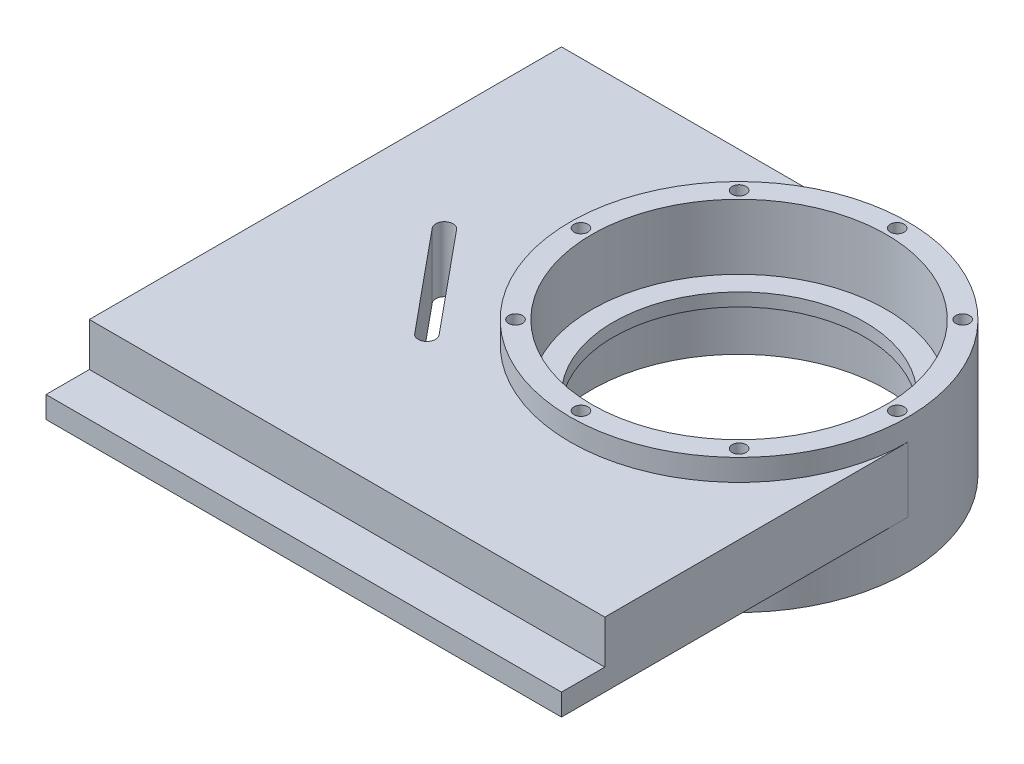
SolidWorks part; units mm, degrees
ref_plane "Front Plane" through (0, 0, 0) normal (0, 0, 1) x (1, 0, 0)
ref_plane "Top Plane" through (0, 0, 0) normal (0, 1, 0) x (1, 0, 0)
ref_plane "Right Plane" through (0, 0, 0) normal (1, 0, 0) x (0, 0, -1)
sketch "Sketch2" plane through (0, 0, 0) normal (0, 1, 0) x (1, 0, 0)
  line L0 (0, 0) -> (0, -80) construction
  line L1 (0, 39) -> (-80, 39)
  line L2 (-80, 39) -> (-80, -80)
  line L3 (-80, -80) -> (0, -80)
  line L4 (39, 0) -> (39, -80)
  line L5 (39, -80) -> (0, -80)
  circle A0 centre (0, 0) radius 22.5 construction
  circle A1 centre (0, 0) radius 34
  circle A2 centre (0, 0) radius 29
  circle A3 centre (0, 0) radius 39
  dimension "D1" = 80
  dimension "D2" = 68
  dimension "D3" = 45
  dimension "D4" = 58
  dimension "D7" = 78
  dimension "D6" = 80
  dimension "D5" = 5
extrude "Boss-Extrude1" add sketch "Sketch2" along normal blind 15 contours A3 A1 region at (26.7972, 0, -26.7972)
extrude "Boss-Extrude2" add sketch "Sketch2<3>" against normal blind 3 contours A3 A1 | A1 A2 region at (26.7972, 0, -26.7972) region at (-33.0383, 0, 0)
sketch "Sketch2<3>" plane through (0, 0, 0) normal (0, 1, 0) x (1, 0, 0) same geometry as "Sketch2"
extrude "Boss-Extrude3" add sketch "Sketch2<4>" against normal blind 16 contours A3 A1 region at (26.7972, 0, -26.7972)
sketch "Sketch2<4>" plane through (0, 0, 0) normal (0, 1, 0) x (1, 0, 0) same geometry as "Sketch2"
extrude "Boss-Extrude4" add sketch "Sketch2<6>" along normal blind 10 and the other way blind 5 contours A3 L1 L2 L3 L5 L4 region at (-33.147, 0, 33.147)
sketch "Sketch2<6>" plane through (0, 0, 0) normal (0, 1, 0) x (1, 0, 0) same geometry as "Sketch2"
sketch "Sketch3" plane through (0, 10, 0) normal (0, 1, 0) x (1, 0, 0)
  line L0 (-80, 39) -> (-80, -80) construction
  line L3 (-80, -70) -> (39, -70)
  line L4 (-80, -70) -> (-80, -80)
  line L5 (-80, -80) -> (39, -80)
  line L6 (39, -70) -> (39, -80)
  point P0 (-80, -70)
  dimension "D1" = 10
extrude "Cut-Extrude1" cut sketch "Sketch3" against normal blind 10
sketch "Sketch4" plane through (0, 15, 0) normal (0, 1, 0) x (1, 0, 0)
  line L0 (0, 34) -> (0, 39) construction
  circle A0 centre (0, 0) radius 34 construction
  circle A1 centre (0, 0) radius 34 construction
  circle A2 centre (0, 0) radius 39 construction
  circle A3 centre (0, 36.5) radius 1.6
  circle A4 centre (25.8094, 25.8094) radius 1.6
  circle A5 centre (36.5, 0) radius 1.6
  circle A6 centre (25.8094, -25.8094) radius 1.6
  circle A7 centre (0, -36.5) radius 1.6
  circle A8 centre (-25.8094, -25.8094) radius 1.6
  circle A9 centre (-36.5, 0) radius 1.6
  circle A10 centre (-25.8094, 25.8094) radius 1.6
  point P27 (0, 0)
  dimension "D1" = 8
extrude "Cut-Extrude2" cut sketch "Sketch4" against normal blind 7
sketch "Sketch5" plane through (0, 10, 0) normal (0, 1, 0) x (1, 0, 0)
  line L0 (-57.1511, -10.8769) -> (-38.0558, -34.015) construction
  line L1 (-57.1511, -10.8769) -> (-38.0558, -34.015) construction
  line L2 (-55.6086, -9.6039) -> (-36.5132, -32.7419)
  line L3 (-58.6936, -12.15) -> (-39.5983, -35.288)
  arc A1 (-55.6086, -9.6039) -> (-58.6936, -12.15) centre (-57.1511, -10.8769) ccw
  arc A8 (-39.5983, -35.288) -> (-36.5132, -32.7419) centre (-38.0558, -34.015) ccw
  point P3 (-47.6034, -22.4459)
  dimension "D1" = 30
  dimension "D2" = 2
extrude "Cut-Extrude3" cut sketch "Sketch5" against normal through all
